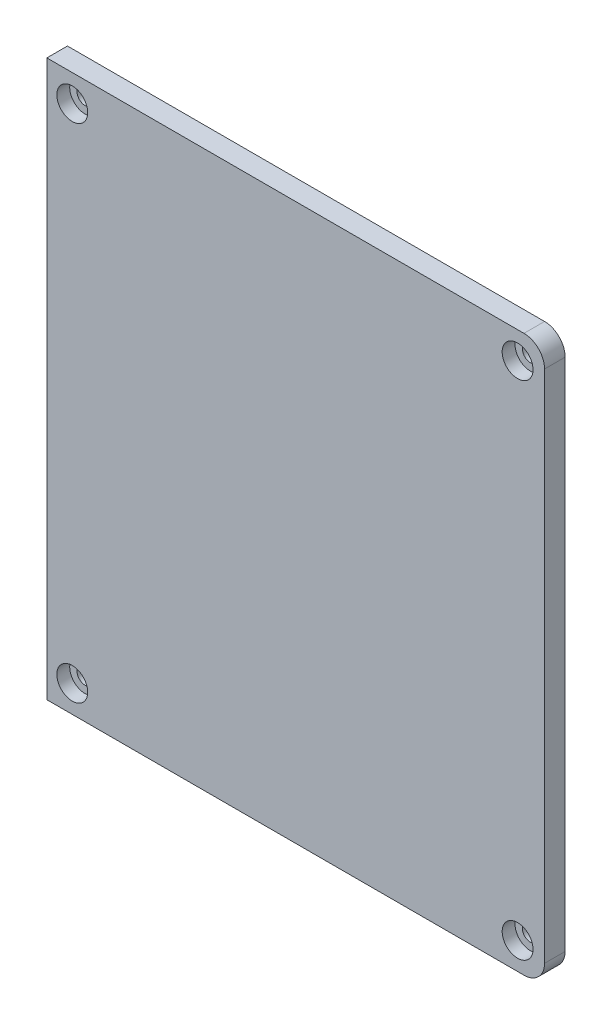
SolidWorks part; units mm, degrees
ref_plane "Front Plane" through (0, 0, 0) normal (0, 0, 1) x (1, 0, 0)
ref_plane "Top Plane" through (0, 0, 0) normal (0, 1, 0) x (1, 0, 0)
ref_plane "Right Plane" through (0, 0, 0) normal (1, 0, 0) x (0, 0, -1)
sketch "Sketch1" plane through (0, 0, 0) normal (0, 0, 1) x (1, 0, 0)
  line L0 (166.6904, 53.1) -> (73.9904, 53.1) construction
  line L1 (73.9904, -54.9) -> (166.6904, -54.9)
  line L2 (73.9904, -54.9) -> (73.9904, 53.1)
  line L3 (73.9904, 53.1) -> (166.6904, 53.1)
  line L4 (170.6904, -50.9) -> (170.6904, 49.1)
  line L5 (170.6904, -50.9) -> (170.6904, 49.1) construction
  line L6 (73.9904, 53.1) -> (73.9904, -54.9) construction
  line L7 (73.9904, -54.9) -> (166.6904, -54.9) construction
  arc A0 (166.6904, -54.9) -> (170.6904, -50.9) centre (166.6904, -50.9) ccw
  arc A1 (166.6904, 53.1) -> (170.6904, 49.1) centre (166.6904, 49.1) cw
  dimension "D1" = 4
extrude "Boss-Extrude1" add sketch "Sketch1" along normal blind 4
sketch "Sketch3" plane through (0, 0, 4) normal (0, 0, 1) x (1, 0, 0)
  circle A0 centre (78.9283, 47.862) radius 1.575
  circle A1 centre (165.4524, 47.862) radius 1.575
  circle A2 centre (165.4524, -49.662) radius 1.575
  circle A3 centre (78.9283, -49.662) radius 1.575
  circle A4 centre (78.9283, -49.662) radius 3
  circle A5 centre (165.4524, -49.662) radius 3
  circle A6 centre (165.4524, 47.862) radius 3
  circle A7 centre (78.9283, 47.862) radius 3
  dimension "D1" = 3.15
  dimension "D2" = 6
extrude "Cut-Extrude1" cut sketch "Sketch3" against normal through all contours A0 | A1 | A2 | A3
extrude "Cut-Extrude2" cut sketch "Sketch3<4>" against normal offset from surface (2.5 mm away) 1.5 up to face at (80.5033, -49.662, 0)
sketch "Sketch3<4>" plane through (0, 0, 4) normal (0, 0, 1) x (1, 0, 0) same geometry as "Sketch3"
